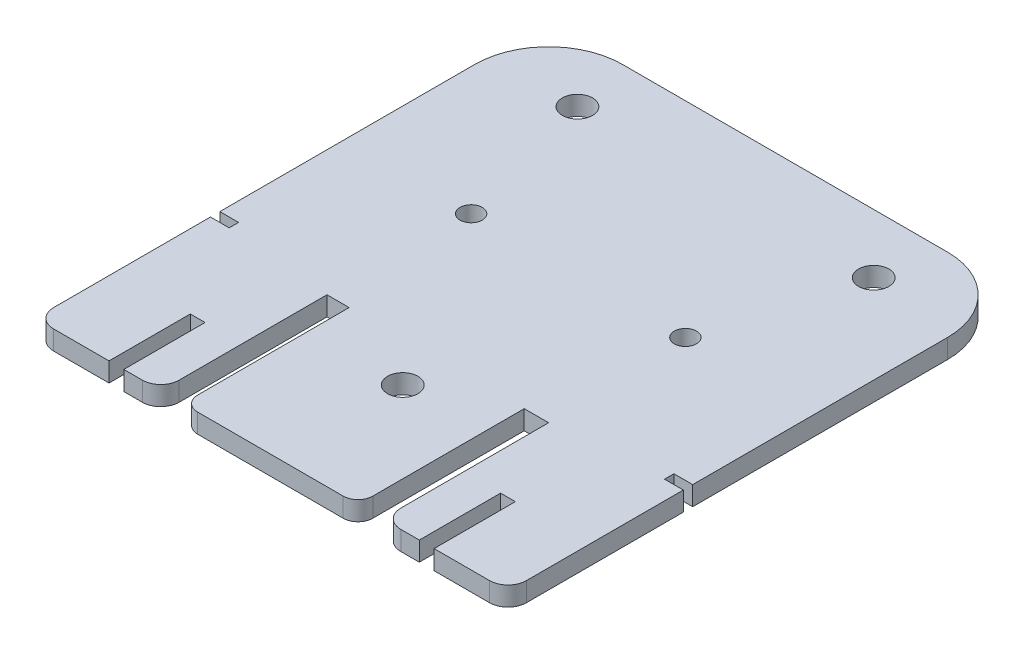
SolidWorks part; units mm, degrees
ref_plane "Front Plane" through (0, 0, 0) normal (0, 0, 1) x (1, 0, 0)
ref_plane "Top Plane" through (0, 0, 0) normal (0, 1, 0) x (1, 0, 0)
ref_plane "Right Plane" through (0, 0, 0) normal (1, 0, 0) x (0, 0, -1)
sketch "Sketch1" plane through (0, 0, 0) normal (0, 1, 0) x (1, 0, 0)
  line L0 (11.7, -23.5) -> (32, -23.5)
  line L1 (-32, -23.5) -> (-12, -23.5)
  line L2 (-32, -23.5) -> (-32, 13.5)
  line L3 (-22, 23.5) -> (22, 23.5)
  line L4 (32, -23.5) -> (32, 13.5)
  line L5 (-32, -23.5) -> (32, 23.5) construction
  line L6 (-32, 23.5) -> (32, -23.5) construction
  line L8 (-12, -23.5) -> (-12, -46)
  line L9 (-12, -46) -> (11.7, -46)
  line L10 (11.7, -23.5) -> (11.7, -46)
  arc A0 (-32, 13.5) -> (-22, 23.5) centre (-22, 13.5) cw
  arc A1 (32, 13.5) -> (22, 23.5) centre (22, 13.5) ccw
  point P0 (0, 0)
  dimension "D6" = 10
  dimension "D7" = 10
  dimension "D1" = 64
  dimension "D2" = 47
  dimension "D3" = 20
  dimension "D4" = 23.7
  dimension "D5" = 22.5
extrude "Main Body" add sketch "Sketch1" along normal blind 2.6
sketch "Sketch2" plane through (0, 2.6, 0) normal (0, 1, 0) x (1, 0, 0)
  line L0 (22, 23.5) -> (-22, 23.5) construction
  line L1 (-32, 13.5) -> (-32, -23.5) construction
  line L2 (0, 0) -> (0, 23.5) construction
  line L3 (32, -23.5) -> (32, 13.5) construction
  line L4 (0.7, -31) -> (0.7, -32.3) construction
  line L5 (0.7, -32.3) -> (14.26, -32.3) construction
  line L6 (-12, -23.5) -> (-12, -46) construction
  line L7 (14.26, -32.3) -> (14.26, -4.25) construction
  line L8 (-14.74, -4.25) -> (-16.24, -4.25) construction
  line L9 (14.26, -4.25) -> (15.76, -4.25) construction
  circle A0 centre (-20.1, 15.5) radius 2.05
  circle A1 centre (20, 15.5) radius 2.05
  circle A3 centre (-14.74, -4.25) radius 1.5
  circle A4 centre (14.26, -4.25) radius 1.5
  circle A6 centre (0.7, -28.95) radius 2.05
  dimension "D1" = 4.1
  dimension "D4" = 4.1
  dimension "D7" = 29
  dimension "D8" = 3
  dimension "D9" = 3
  dimension "D10" = 13.56
  dimension "D11" = 4.1
  dimension "D2" = 8
  dimension "D3" = 11.9
  dimension "D5" = 8
  dimension "D6" = 12
  dimension "D12" = 28.05
  dimension "D13" = 1.3
  dimension "D20" = 12.7
  dimension "D21" = 44.45
extrude "Screw holes" cut sketch "Sketch2" against normal through all both and the other way through all
fillet "Main lower body Fillet" radius 2 2 edges at (11.7, 1.3, 46) (-12, 1.3, 46)
sketch "Sketch4" plane through (0, 2.6, 0) normal (0, 1, 0) x (1, 0, 0)
  line L1 (-32, -23.5) -> (-15, -23.5)
  line L2 (-32, -23.5) -> (-32, -21)
  line L3 (-32, -21) -> (-15, -21)
  line L4 (-15, -23.5) -> (-15, -21)
  line L5 (32, -23.5) -> (15, -23.5)
  line L6 (32, -23.5) -> (32, -21)
  line L7 (32, -21) -> (15, -21)
  line L8 (15, -23.5) -> (15, -21)
  dimension "D1" = 2.5
  dimension "D2" = 2.5
  dimension "D3" = 17
  dimension "D4" = 17
sketch "Sketch5" plane through (0, 0, 23.5) normal (0, 0, 1) x (1, 0, 0)
  line L0 (-32, 0) -> (-12, 0) construction
  line L1 (-32, 2.6) -> (-15, 2.6)
  line L2 (-32, 2.6) -> (-32, 0)
  line L3 (-32, 0) -> (-15, 0)
  line L4 (-15, 2.6) -> (-15, 0)
  line L5 (11.7, 0) -> (32, 0) construction
  line L6 (32, 2.6) -> (15, 2.6)
  line L7 (32, 2.6) -> (32, 0)
  line L8 (32, 0) -> (15, 0)
  line L9 (15, 2.6) -> (15, 0)
  dimension "D1" = 17
  dimension "D2" = 17
extrude "Boss-Extrude1" add sketch "Sketch5" along normal blind 22.5
sketch "Sketch6" plane through (0, 2.6, 0) normal (0, 1, 0) x (1, 0, 0)
  line L0 (-15, -46) -> (-32, -46) construction
  line L1 (-20, -46) -> (-22, -46)
  line L2 (-20, -46) -> (-20, -35)
  line L3 (-20, -35) -> (-22, -35)
  line L4 (-22, -46) -> (-22, -35)
  line L5 (32, -46) -> (15, -46) construction
  line L6 (22, -46) -> (20, -46)
  line L7 (22, -46) -> (22, -35)
  line L8 (22, -35) -> (20, -35)
  line L9 (20, -46) -> (20, -35)
  line L10 (-32, 13.5) -> (-32, -46) construction
  line L11 (32, -46) -> (32, 13.5) construction
  point P16 (21, -35)
  dimension "D1" = 12
  dimension "D2" = 12
  dimension "D3" = 10
  dimension "D4" = 10
  dimension "D5" = 11
  dimension "D6" = 11
extrude "Cut-Extrude1" cut sketch "Sketch6" against normal blind 22.5
fillet "Fillet2" radius 2.5 4 edges at (-32, 1.3, 46) (-15, 1.3, 46) (15, 1.3, 46) (32, 1.3, 46)
sketch "Sketch7" plane through (0, 2.6, 0) normal (0, 1, 0) x (1, 0, 0)
  line L1 (-32, -21) -> (-29.46, -21)
  line L2 (-32, -21) -> (-32, -22.27)
  line L3 (-32, -22.27) -> (-29.46, -22.27)
  line L4 (-29.46, -21) -> (-29.46, -22.27)
  line L5 (32, -21) -> (29.46, -21)
  line L6 (32, -21) -> (32, -22.27)
  line L7 (32, -22.27) -> (29.46, -22.27)
  line L8 (29.46, -21) -> (29.46, -22.27)
  dimension "D1" = 2.54
  dimension "D2" = 2.54
  dimension "D3" = 1.27
  dimension "D4" = 1.27
extrude "Cut-Extrude2" cut sketch "Sketch7" against normal through all
